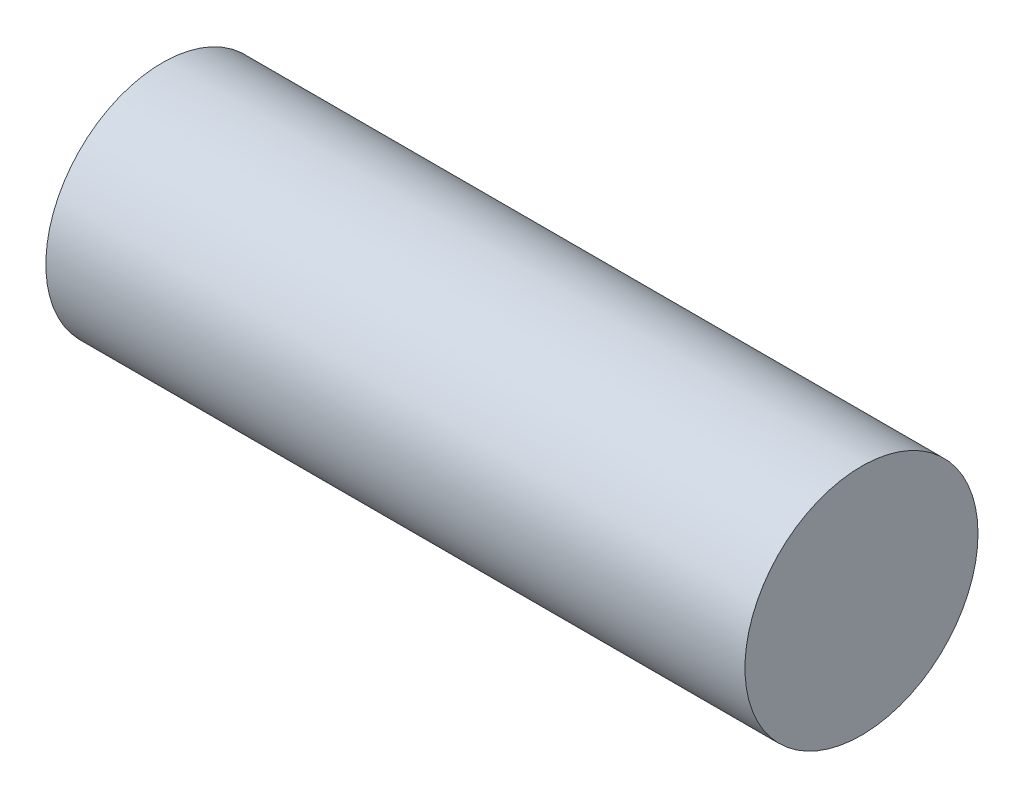
SolidWorks part; units mm, degrees
material "AISI 4340 Steel, normalized"
ref_plane "Front Plane" through (0, 0, 0) normal (0, 0, 1) x (1, 0, 0)
ref_plane "Top Plane" through (0, 0, 0) normal (0, 1, 0) x (1, 0, 0)
ref_plane "Right Plane" through (0, 0, 0) normal (1, 0, 0) x (0, 0, -1)
sketch "Sketch1" plane through (0, 0, 0) normal (1, 0, 0) x (0, 0, -1)
  circle A0 centre (0, 0) radius 38.1
  dimension "D1" = 76.2
extrude "Boss-Extrude1" add sketch "Sketch1" along normal blind 228.6
